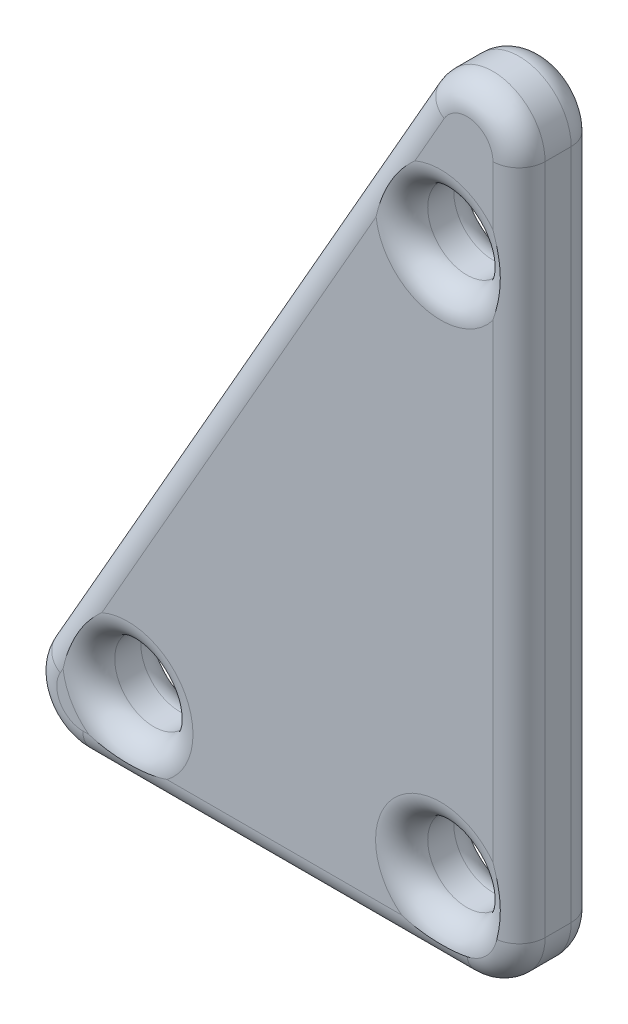
SolidWorks part; units mm, degrees
ref_plane "Front Plane" through (0, 0, 0) normal (0, 0, 1) x (1, 0, 0)
ref_plane "Top Plane" through (0, 0, 0) normal (0, 1, 0) x (1, 0, 0)
ref_plane "Right Plane" through (0, 0, 0) normal (1, 0, 0) x (0, 0, -1)
sketch "Sketch1" plane through (0, 0, 0) normal (0, 0, 1) x (1, 0, 0)
  line L0 (0, 21) -> (0, -0.9209) construction
  line L1 (0, 0) -> (-12, 0) construction
  line L2 (0, 21) -> (-12, 0) construction
  line L3 (3, 24.7656) -> (3, -1)
  line L4 (-0.7365, 25.7578) -> (-15.4597, -0.0077)
  line L5 (3, 32.2967) -> (-14.6047, 1.4884) construction
  line L6 (3, 32.2967) -> (3, -0.9209) construction
  line L7 (1, -3) -> (-12, -3)
  line L8 (0, -3) -> (-12, -3) construction
  line L9 (-12, -3) -> (-13.7232, -3)
  circle A0 centre (0, 0) radius 1.5
  circle A1 centre (0, 21) radius 1.5
  circle A2 centre (-12, 0) radius 1.5
  arc A3 (-13.7232, -3) -> (-15.4597, -0.0077) centre (-13.7232, -1) cw
  arc A4 (1, -3) -> (3, -1) centre (1, -1) ccw
  arc A5 (3, 24.7656) -> (-0.7365, 25.7578) centre (1, 24.7656) ccw
  point P11 (0, 0)
  point P13 (6.6138, -3)
  dimension "D1" = 3
  dimension "D2" = 3
  dimension "D3" = 3
  dimension "D8" = 2
  dimension "D4" = 21
  dimension "D5" = 12
  dimension "D6" = 3
  dimension "D7" = 3
extrude "Boss-Extrude1" add sketch "Sketch1" along normal blind 3
fillet "Fillet1" radius 1 18 edges at (-15.453, -2.0039, 3) (-15.453, -2.0039, 0) (-6.3616, -3, 3) (-6.3616, -3, 0) (2.4142, -2.4142, 3) (2.4142, -2.4142, 0) (3, 11.8828, 3) (3, 11.8828, 0) (1.5133, 26.6986, 3) (1.5133, 26.6986, 0) (-8.0981, 12.8751, 3) (-8.0981, 12.8751, 0) (1.5, 21, 0) (1.5, 21, 3) (1.5, 0, 0) (1.5, 0, 3) (-10.5, 0, 0) (-10.5, 0, 3)
